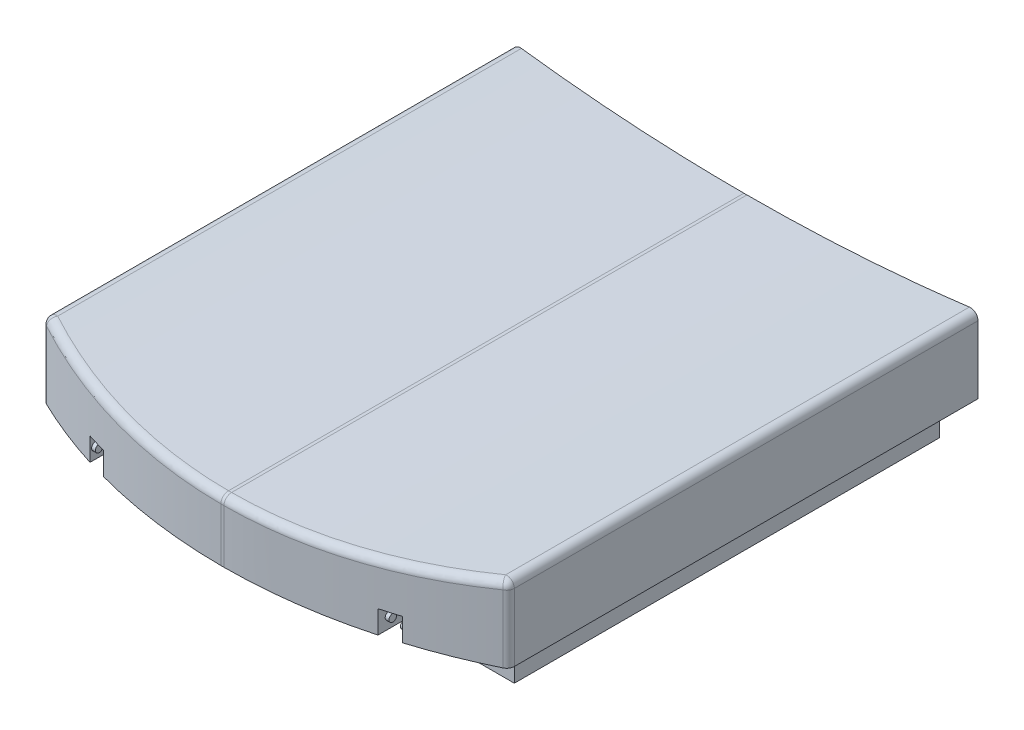
SolidWorks part; units mm, degrees
ref_plane "Front Plane" through (0, 0, 0) normal (0, 0, 1) x (1, 0, 0)
ref_plane "Top Plane" through (0, 0, 0) normal (0, 1, 0) x (1, 0, 0)
ref_plane "Right Plane" through (0, 0, 0) normal (1, 0, 0) x (0, 0, -1)
sketch "Sketch1" plane through (0, 0, 0) normal (0, 1, 0) x (1, 0, 0)
  line L1 (-305, 342.9) -> (305, 342.9)
  line L2 (-305, 342.9) -> (-305, -342.9)
  line L3 (-305, -342.9) -> (305, -342.9)
  line L4 (305, 342.9) -> (305, -342.9)
  line L5 (-305, 342.9) -> (305, -342.9) construction
  line L6 (-305, -342.9) -> (305, 342.9) construction
  point P0 (0, 0)
  dimension "D1" = 610
  dimension "D2" = 685.8
extrude "Boss-Extrude1" add sketch "Sketch1" along normal blind 100
sketch "Sketch2" plane through (0, 0, 0) normal (0, 0, 1) x (1, 0, 0)
  line L0 (0, 100) -> (0, 80) construction
  line L1 (0, -55) -> (0, 55) construction
  line L2 (-305, 100) -> (305, 100) construction
  line L3 (0, 80) -> (2, 80)
  line L4 (0, 80) -> (-2, 80)
  line L5 (-305, 100) -> (305, 100)
  spline S0 degree 2 poles (305, 100) (153.8297, 80) (2, 80) knots 0 0 0 1 1 1
  spline S1 degree 2 poles (-2, 80) (-153.8297, 80) (-305, 100) knots 0 0 0 1 1 1
  dimension "D1" = 2
  dimension "D2" = 20
extrude "Cut-Extrude1" cut sketch "Sketch2" against normal mid plane 700
sketch "Sketch5" plane through (0, 0, 0) normal (0, 1, 0) x (1, 0, 0)
  line L13 (-2, 342.9) -> (2, 342.9) construction
  line L14 (2, -342.9) -> (-2, -342.9) construction
  line L15 (-305, -342.9) -> (-2, -342.9) construction
  line L16 (-305, 342.9) -> (-305, -342.9) construction
  line L17 (2, 342.9) -> (2, -342.9) construction
  line L18 (305, -342.9) -> (305, 342.9) construction
  line L19 (305, -271.348) -> (305, -393.2789)
  line L20 (305, -393.2789) -> (-305, -393.2789)
  line L21 (-305, -393.2789) -> (-305, -271.348)
  line L22 (-2, -342.9) -> (2, -342.9)
  arc A0 (-2, -342.9) -> (-305, -271.348) centre (0, 342.9) cw
  arc A1 (2, -342.9) -> (305, -271.348) centre (0, 342.9) ccw
  dimension "D1" = 685.8029
  dimension "D2" = 121.9308
extrude "Cut-Extrude2" cut sketch "Sketch5" along normal blind 100
fillet "Fillet1" radius 10 7 edges at (0, 80, 342.9) (305, 100, -35.776) (-305, 100, -35.776) (305, 50, 271.348) (-305, 50, 271.348) (201.4562, 88.6535, 312.6464) (-78.2311, 81.2618, 338.4263)
sketch "Sketch6" plane through (0, 0, 0) normal (0, 1, 0) x (1, 0, 0)
  line L0 (-305, 342.9) -> (-305, -265.1169) construction
  line L1 (-205, -319.48) -> (-180, -319.48)
  line L2 (-205, -319.48) -> (-205, -284.48)
  line L3 (-205, -284.48) -> (-180, -284.48)
  line L4 (-180, -319.48) -> (-180, -284.48)
  line L5 (-205, -319.48) -> (-180, -284.48) construction
  line L6 (-205, -284.48) -> (-180, -319.48) construction
  line L7 (305, 342.9) -> (-305, 342.9) construction
  point P0 (-192.5, -301.98)
  dimension "D1" = 25
  dimension "D2" = 35
  dimension "D3" = 100
  dimension "D4" = 627.38
extrude "Cut-Extrude3" cut sketch "Sketch6" along normal blind 30
sketch "Sketch7" plane through (-180, 0, 0) normal (-1, 0, 0) x (0, 0, 1)
  circle A0 centre (304.48, 15) radius 5
  point P10 (0, 0)
  dimension "D1" = 10
  dimension "D2" = 304.48
  dimension "D3" = 15
extrude "Boss-Extrude2" add sketch "Sketch7" along normal blind 5
sketch "Sketch8" plane through (-205, 0, 0) normal (1, 0, 0) x (0, 0, -1)
  line L0 (-304.48, 30) -> (-304.48, 12.7746) construction
  line L2 (-284.48, 15) -> (-237.3973, 15) construction
  line L3 (-284.48, 30) -> (-284.48, 0) construction
  circle A0 centre (-304.48, 15) radius 5
  dimension "D1" = 10
  dimension "D2" = 20
extrude "Boss-Extrude3" add sketch "Sketch8" along normal blind 5
mirror "Mirror1" about plane through (0, 0, 0) normal (1, 0, 0) of "Boss-Extrude3", "Cut-Extrude3", "Boss-Extrude2"
sketch "Sketch9" plane through (0, 0, 0) normal (0, -1, 0) x (1, 0, 0)
  line L0 (-305, -342.9) -> (-305, 265.1169) construction
  line L3 (-254.2, 214.3169) -> (-254.2, -342.9)
  line L4 (305, -342.9) -> (-305, -342.9) construction
  line L5 (-254.2, -342.9) -> (-222.45, -342.9)
  line L6 (-222.45, -342.9) -> (-222.45, 182.5669)
  line L7 (-222.45, 182.5669) -> (-125.93, 182.5669)
  line L8 (-125.93, 182.5669) -> (-125.93, -342.9)
  line L9 (-125.93, -342.9) -> (125.93, -342.9)
  line L10 (222.45, 182.5669) -> (222.45, -342.9)
  line L12 (-254.2, 214.3169) -> (254.2, 214.3169)
  line L13 (125.93, 182.5669) -> (125.93, -342.9)
  line L14 (222.45, 182.5669) -> (125.93, 182.5669)
  line L18 (222.45, -342.9) -> (254.2, -342.9)
  line L19 (254.2, -342.9) -> (254.2, 214.3169)
  point P20 (0, 214.3169)
  dimension "D1" = 50.8
  dimension "D2" = 31.75
  dimension "D3" = 50.8
  dimension "D4" = 31.75
  dimension "D5" = 222.45
  dimension "D8" = 96.52
  dimension "D9" = 31.75
  dimension "D10" = 31.75
  dimension "D11" = 251.86
extrude "Boss-Extrude4" add sketch "Sketch9" along normal blind 69.85
